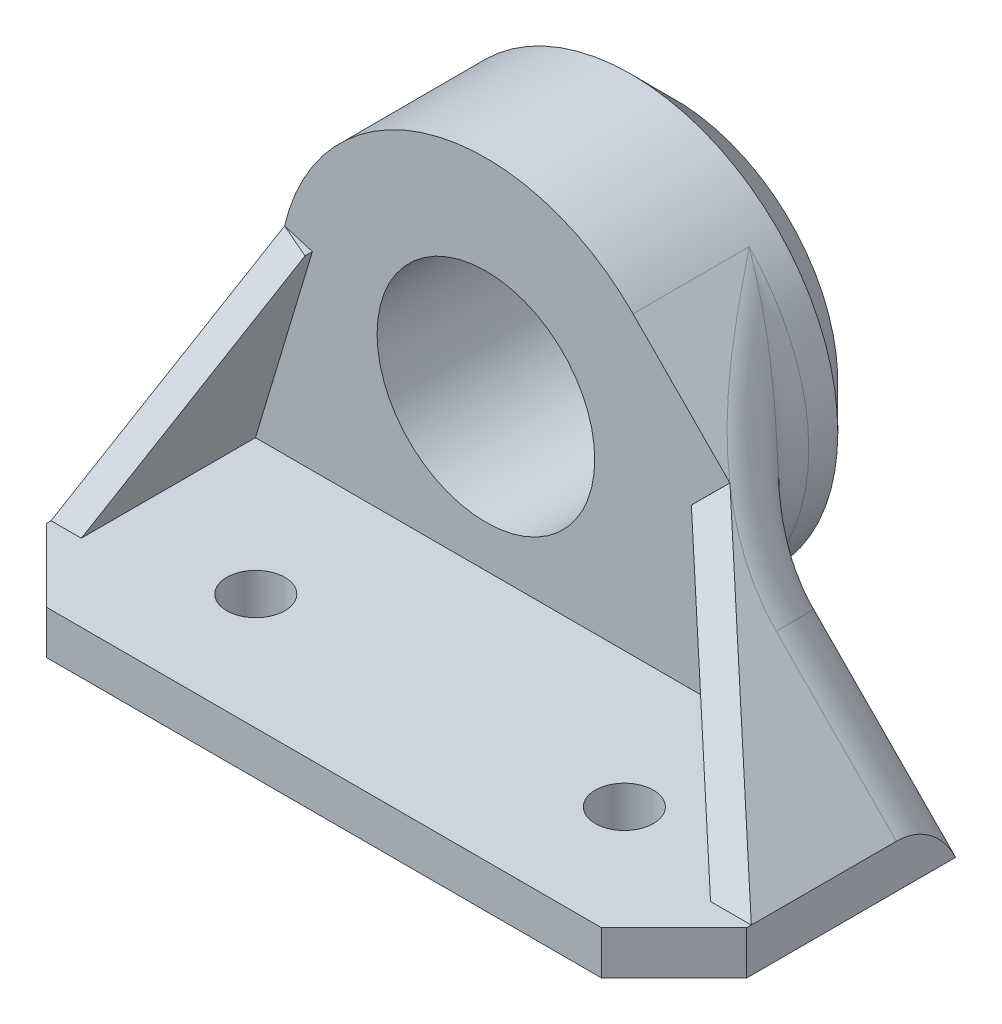
SolidWorks part; units mm, degrees
ref_plane "Front Plane" through (0, 0, 0) normal (0, 0, 1) x (1, 0, 0)
ref_plane "Top Plane" through (0, 0, 0) normal (0, 1, 0) x (1, 0, 0)
ref_plane "Right Plane" through (0, 0, 0) normal (1, 0, 0) x (0, 0, -1)
sketch "Sketch1" plane through (0, 0, 0) normal (0, 1, 0) x (1, 0, 0)
  line L1 (-24.13, 10.16) -> (24.13, 10.16)
  line L2 (-24.13, 10.16) -> (-24.13, -10.16)
  line L3 (-24.13, -10.16) -> (24.13, -10.16)
  line L4 (24.13, 10.16) -> (24.13, -10.16)
  line L5 (-24.13, 10.16) -> (24.13, -10.16) construction
  line L6 (-24.13, -10.16) -> (24.13, 10.16) construction
  point P0 (0, 0)
  dimension "D1" = 48.26
  dimension "D2" = 20.32
extrude "Boss-Extrude1" add sketch "Sketch1" along normal blind 3
sketch "Sketch2" plane through (0, 3, 0) normal (0, 1, 0) x (1, 0, 0)
  line L0 (-24.13, 10.16) -> (-24.13, -10.16) construction
  line L1 (-24.13, -10.16) -> (24.13, -10.16) construction
  circle A0 centre (-12.7, -2.16) radius 2
  circle A1 centre (12.7, -2.16) radius 2
  dimension "D1" = 4
  dimension "D2" = 4
  dimension "D3" = 25.4
  dimension "D4" = 11.43
  dimension "D5" = 8
  dimension "D6" = 8
extrude "Cut-Extrude1" cut sketch "Sketch2" against normal blind 3
chamfer "Chamfer1" distance 5 angle 45 2 edges at (24.13, 1.5, 10.16) (-24.13, 1.5, 10.16)
sketch "Sketch3" plane through (0, 0, -10.16) normal (0, 0, -1) x (-1, 0, 0)
  line L0 (-24.13, 3) -> (24.13, 3) construction
  line L4 (24.13, 3) -> (24.13, 0) construction
  circle A0 centre (6.16, 13.39) radius 11.25
  circle A1 centre (6.16, 13.39) radius 14.25
  dimension "D1" = 22.5
  dimension "D2" = 10.39
  dimension "D3" = 17.97
  dimension "D4" = 3
extrude "Boss-Extrude2" add sketch "Sketch3" along normal blind 10
sketch "Sketch4" plane through (0, 0, -10.16) normal (0, 0, 1) x (1, 0, 0)
  circle A0 centre (-6.16, 13.39) radius 14.25
extrude "Boss-Extrude3" add sketch "Sketch4" along normal blind 3
sketch "Sketch5" plane through (0, 0, -7.16) normal (0, 0, 1) x (1, 0, 0)
  line L0 (-24.13, 3) -> (-20.0341, 16.6413)
  line L1 (-24.13, 3) -> (24.13, 3)
  line L2 (24.13, 3) -> (3.9787, 23.4034)
  line L3 (-20.0341, 16.6413) -> (3.9787, 23.4034)
  arc A0 (3.5925, 3) -> (-15.9125, 3) centre (-6.16, 13.39) ccw construction
extrude "Boss-Extrude4" add sketch "Sketch5" against normal blind 3
sketch "Sketch6" plane through (0, 0, -7.16) normal (0, 0, 1) x (1, 0, 0)
  line L0 (-24.13, 3) -> (-20.0341, 16.6413)
  line L1 (-20.0341, 16.6413) -> (-18.1186, 16.0662)
  line L2 (-18.1186, 16.0662) -> (-22.0418, 3)
  line L3 (-24.13, 3) -> (24.13, 3) construction
  line L4 (-22.0418, 3) -> (-24.13, 3)
  line L5 (24.13, 3) -> (10.6572, 16.6413)
  line L7 (10.6572, 16.6413) -> (9.2343, 15.236)
  line L8 (9.2343, 15.236) -> (21.319, 3)
  line L9 (19.13, 3) -> (24.13, 3) construction
  line L10 (21.319, 3) -> (24.13, 3)
  line L11 (24.13, 3) -> (3.9787, 23.4034) construction
  dimension "D1" = 2
  dimension "D2" = 2
  dimension "D3" = 0
  dimension "D4" = 0
extrude "Boss-Extrude5" add sketch "Sketch6" along normal blind 12
sketch "Sketch9" plane through (-24.13, 0, 0) normal (-1, 0, 0) x (0, 0, 1)
  line L0 (-7.16, 16.6413) -> (4.84, 3)
  line L1 (4.84, 3) -> (4.84, 16.6413)
  line L2 (4.84, 16.6413) -> (-7.16, 16.6413)
extrude "Cut-Extrude2" cut sketch "Sketch9" against normal blind 12
sketch "Sketch10" plane through (24.13, 0, 0) normal (1, 0, 0) x (0, 0, -1)
  line L0 (-4.84, 3) -> (7.16, 16.6413)
  line L1 (7.16, 16.6413) -> (-4.84, 16.6413)
  line L2 (-4.84, 16.6413) -> (-4.84, 3)
extrude "Cut-Extrude3" cut sketch "Sketch10" against normal blind 22
sketch "Sketch11" plane through (0, 0, -10.16) normal (0, 0, -1) x (-1, 0, 0)
  circle A0 centre (6.16, 13.39) radius 5
  dimension "D1" = 10
extrude "Cut-Extrude4" cut sketch "Sketch11" against normal blind 22
sketch "Sketch12" plane through (0, 0, 10.16) normal (0, 0, 1) x (1, 0, 0)
  line L0 (-19.13, 0) -> (19.13, 0) construction
  line L1 (-14.7547, 0) -> (3.1434, 0)
  line L2 (-14.7547, 0) -> (-14.7547, -4.4552)
  line L3 (-14.7547, -4.4552) -> (3.1434, -4.4552)
  line L4 (3.1434, 0) -> (3.1434, -4.4552)
extrude "Cut-Extrude5" cut sketch "Sketch12" against normal blind 52
fillet "Fillet2" radius 5 2 edges at (-18.6948, 6.612, -10.16) (7.7428, 10.2634, -10.16)
fillet "Fillet3" radius 5 3 edges at (10.0701, 17.2359, -10.8713) (-20.1963, 16.1012, -14.4852) (18.6016, 8.5976, -10.16)
sketch "Sketch13" plane through (0, 0, -10.16) normal (0, 0, -1) x (-1, 0, 0)
  circle A0 centre (6.16, 13.39) radius 7.5
  dimension "D1" = 15
extrude "Cut-Extrude6" cut sketch "Sketch13" against normal blind 10
sketch "Sketch14" plane through (0, 0, -10.16) normal (0, 0, -1) x (-1, 0, 0)
  circle A0 centre (6.16, 13.39) radius 7.5
  circle A1 centre (6.16, 13.39) radius 11.25
extrude "Boss-Extrude6" add sketch "Sketch14" along normal blind 10
chamfer "Chamfer2" distance 3 angle 45 1 edges at (-6.16, 27.64, -20.16)
